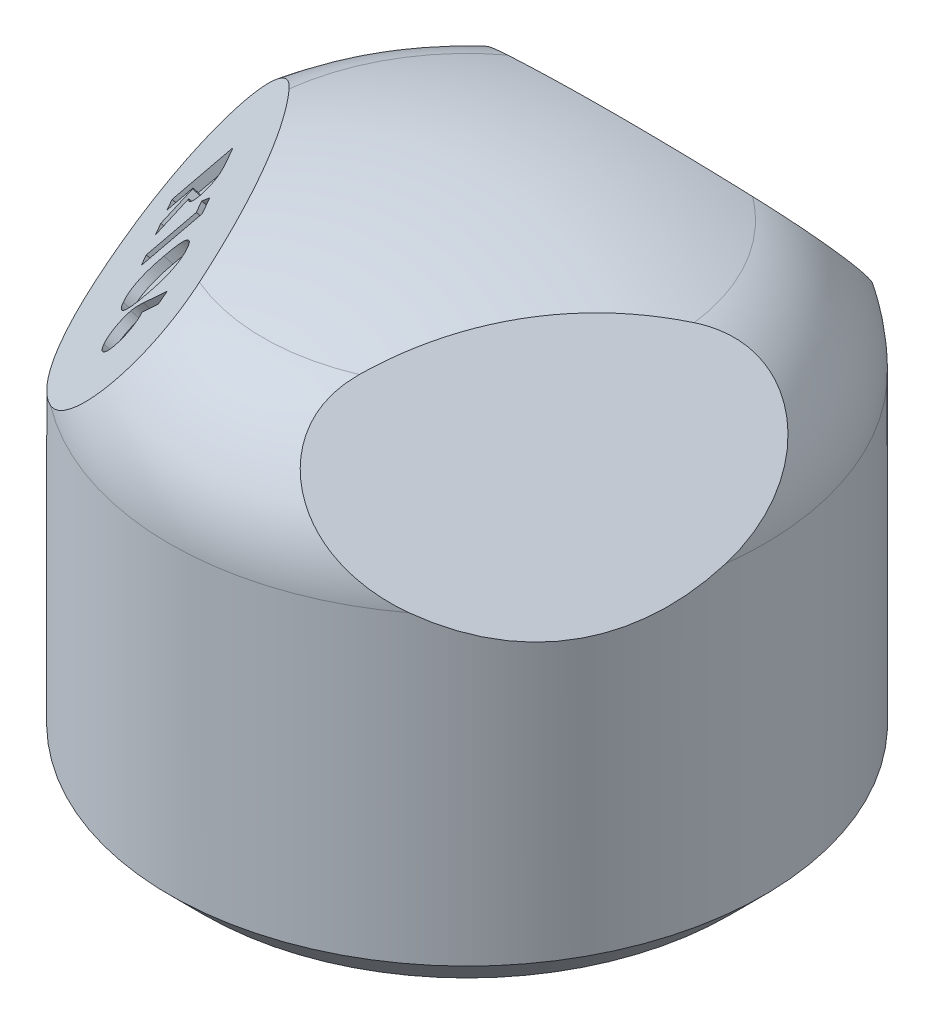
SolidWorks part; units mm, degrees
note: '?' marks a value the reader was unsure of.
ref_plane "Ebene vorne" through (0, 0, 0) normal (0, 0, 1) x (1, 0, 0)
ref_plane "Ebene oben" through (0, 0, 0) normal (0, 1, 0) x (1, 0, 0)
ref_plane "Ebene rechts" through (0, 0, 0) normal (1, 0, 0) x (0, 0, -1)
sketch "Skizze1" plane through (0, 0, 0) normal (0, 0, 1) x (1, 0, 0)
  line L3 (0, 0) -> (0, 30)
  line L4 (0, 0) -> (-3.5532, 0) construction
  line L5 (0, 0) -> (21.6511, 0)
  line L7 (17, 3.0667) -> (15, 1.0667)
  line L8 (17, 3.0667) -> (17, 25.5941)
  line L9 (0, 30) -> (-3.7069, 30) construction
  arc A0 (15, 1.0667) -> (0, 0) centre (0, 106) cw
  arc A1 (0, 30) -> (17, 25.5941) centre (0, -5) cw
  dimension "D1" = 106
  dimension "D6" = 35
  dimension "D2" = 17
  dimension "D3" = 30
  dimension "D4" = 15
  dimension "D5" = 135
revolve "Rotation1" add sketch "Skizze1" angle 360 about L3
fillet "Verrundung1" radius 8 1 edges at (0, 25.5941, -17)
sketch "Skizze10" plane through (0, 0, 0) normal (-1, 0, 0) x (0, -1, 0)
  line L0 (-30.099, -7.5633) -> (-17.7607, -17.9163)
  line L1 (-17.7607, -17.9163) -> (-30.099, -17.9163)
  line L2 (-30.099, -17.9163) -> (-30.099, -7.5633)
  dimension "D1" = 40
extrude "Schnitt-Linear austragen2" cut sketch "Skizze10" against normal through all both and the other way through all
ref_axis "Achse2" through (0, 20.4558, 0) along (0, -1, 0)?
pattern_circular "Kreismuster3" count 3 over 360 about axis through (0, 0, 0) along (0, 1, 0) of "Schnitt-Linear austragen2"
sketch "Skizze11" plane through (-46.6919, -25.1411, 26.9576) normal (0.6634, -0.6428, -0.383) x (-0.2321, -0.6634, 0.7113)
  line L0 (-39.9732, -55.3314) -> (-67.9791, -6.8236) construction
  line L1 (-60.2626, -34.7926) -> (-48.7264, -28.1322) construction
  text T0 "<b>R106</b>" font "Century Gothic" height 4
extrude "Schnitt-Linear austragen3" cut sketch "Skizze11" along normal blind 0.5
sketch "Skizze12" plane through (-16.6789, 16.1604, 9.6296) normal (-0.6634, 0.6428, 0.383) x (0.2751, -0.2665, 0.9237)
  circle A0 centre (-8.2651, 8.8842) radius 0.9367
  circle A1 centre (1.0167, 10.5271) radius 0.9496
  ellipse E0 centre (-1.9495, 10.2183) end of major axis (-1.3676, 8.6997) minor radius 1.0549
extrude "Schnitt-Linear austragen4" cut sketch "Skizze12" against normal blind 0.5
other "Körper speichern1"
